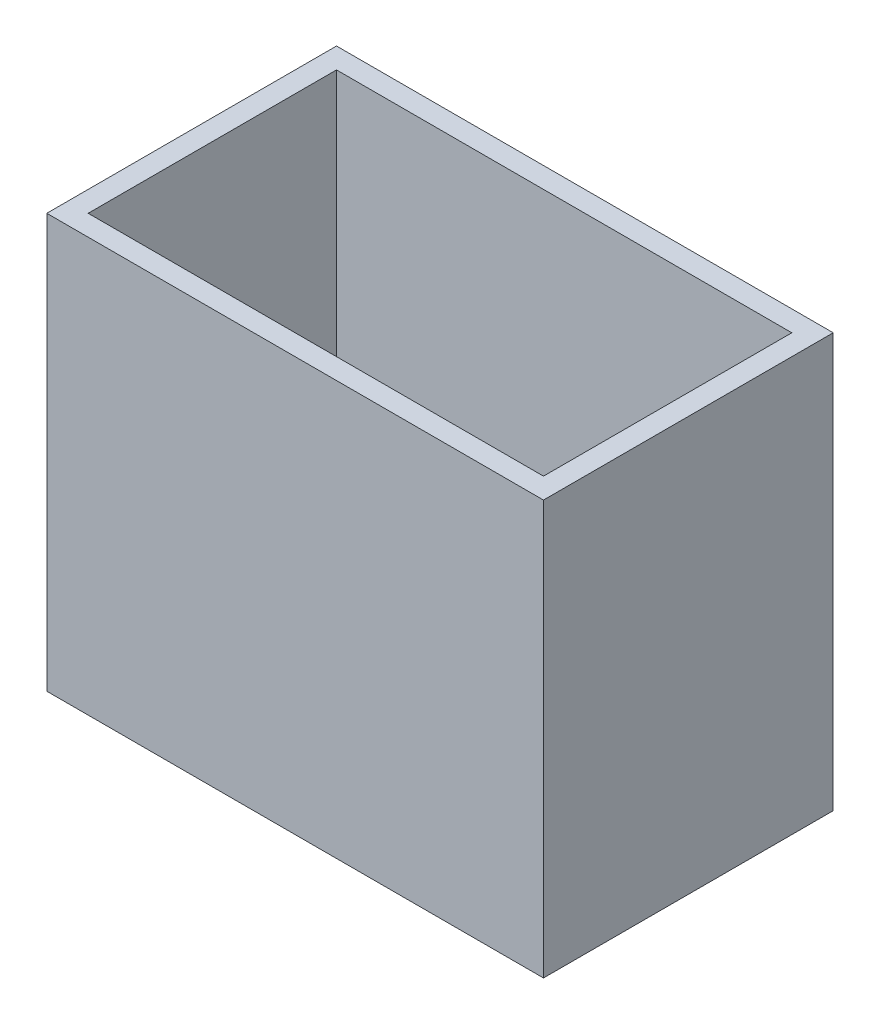
SolidWorks part; units mm, degrees
ref_plane "前视基准面" through (0, 0, 0) normal (0, 0, 1) x (1, 0, 0)
ref_plane "上视基准面" through (0, 0, 0) normal (0, 1, 0) x (1, 0, 0)
ref_plane "右视基准面" through (0, 0, 0) normal (1, 0, 0) x (0, 0, -1)
sketch "草图1" plane through (0, 0, 0) normal (0, 1, 0) x (1, 0, 0)
  line L1 (60, -35) -> (-60, -35)
  line L2 (60, -35) -> (60, 35)
  line L3 (60, 35) -> (-60, 35)
  line L4 (-60, -35) -> (-60, 35)
  line L5 (60, -35) -> (-60, 35) construction
  line L6 (60, 35) -> (-60, -35) construction
  point P0 (0, 0)
  dimension "D1" = 120
  dimension "D2" = 70
extrude "凸台-拉伸1" add sketch "草图1" along normal blind 100
shell "抽壳1" thickness 5 removed face at (0, 100, 0)
